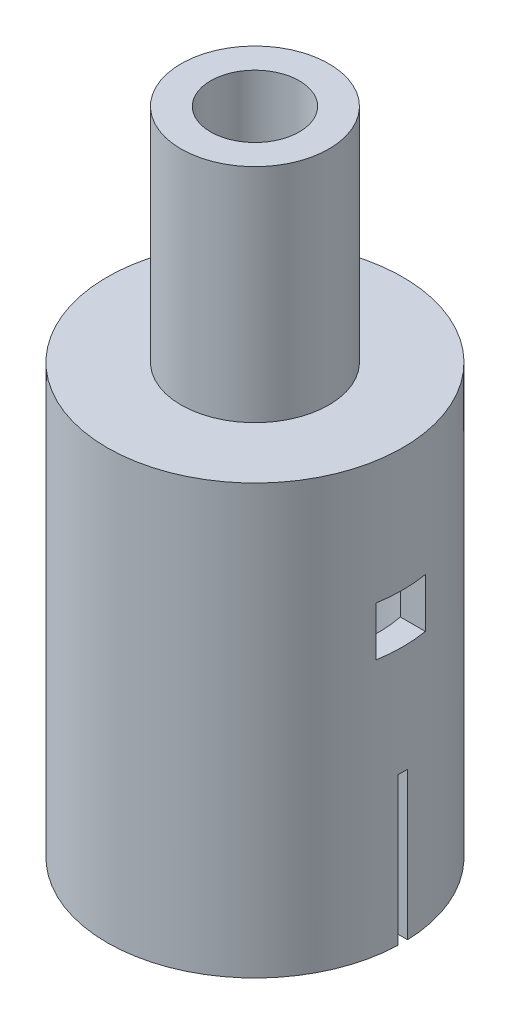
SolidWorks part; units mm, degrees
ref_plane "Front Plane" through (0, 0, 0) normal (0, 0, 1) x (1, 0, 0)
ref_plane "Top Plane" through (0, 0, 0) normal (0, 1, 0) x (1, 0, 0)
ref_plane "Right Plane" through (0, 0, 0) normal (1, 0, 0) x (0, 0, -1)
sketch "Sketch2" plane through (0, 0, 0) normal (0, 1, 0) x (1, 0, 0)
  circle A0 centre (0, 0) radius 7.62
  dimension "D1" = 15.24
extrude "Boss-Extrude1" add sketch "Sketch2" against normal blind 22.098 contours A0
sketch "Sketch3" plane through (0, -22.098, 0) normal (0, -1, 0) x (1, 0, 0)
  circle A0 centre (0, 0) radius 6.35
  dimension "D1" = 12.7
extrude "Cut-Extrude1" cut sketch "Sketch3" against normal blind 16.764
sketch "Sketch5" plane through (0, 0, 0) normal (0, 1, 0) x (1, 0, 0)
  circle A0 centre (0, 0) radius 2.3495
  dimension "D1" = 4.699
extrude "Cut-Extrude3" cut sketch "Sketch5" along normal blind 16.764 and the other way through all contours A0
sketch "Sketch6" plane through (0, 0, 0) normal (0, 1, 0) x (1, 0, 0)
  circle A0 centre (0, 0) radius 3.81
  dimension "D1" = 7.62
extrude "Boss-Extrude2" add sketch "Sketch6" along normal blind 11.43 contours A0
sketch "Sketch8" plane through (0, 11.43, 0) normal (0, 1, 0) x (1, 0, 0)
  circle A0 centre (0, 0) radius 2.286
  dimension "D1" = 4.572
extrude "Cut-Extrude4" cut sketch "Sketch8" against normal blind 11.176 contours A0
sketch "Sketch10" plane through (0, 0, 0) normal (0, -1, 0) x (1, 0, 0)
  circle A0 centre (0, 0) radius 1.7198
extrude "Cut-Extrude8" cut sketch "Sketch10" against normal up to next
sketch "Sketch12" plane through (0, 0, 0) normal (1, 0, 0) x (0, 0, -1)
  line L0 (7.62, 0) -> (-7.62, 0) construction
  line L1 (-1.27, -6.35) -> (1.27, -6.35)
  line L2 (-1.27, -6.35) -> (-1.27, -8.89)
  line L3 (-1.27, -8.89) -> (1.27, -8.89)
  line L4 (1.27, -6.35) -> (1.27, -8.89)
  line L5 (-1.27, -6.35) -> (1.27, -8.89) construction
  line L6 (-1.27, -8.89) -> (1.27, -6.35) construction
  point P0 (0, -7.62)
  dimension "D1" = 2.54
  dimension "D2" = 2.54
  dimension "D3" = 7.62
extrude "Cut-Extrude10" cut sketch "Sketch12" against normal through all both and the other way through all
sketch "Sketch16" plane through (0, -22.098, 0) normal (0, -1, 0) x (1, 0, 0)
  line L1 (-11.0491, -0.254) -> (11.0491, -0.254)
  line L2 (-11.0491, -0.254) -> (-11.0491, 0.254)
  line L3 (-11.0491, 0.254) -> (11.0491, 0.254)
  line L4 (11.0491, -0.254) -> (11.0491, 0.254)
  line L5 (-11.0491, -0.254) -> (11.0491, 0.254) construction
  line L6 (-11.0491, 0.254) -> (11.0491, -0.254) construction
  point P0 (0, 0)
  dimension "D1" = 0.508
extrude "Cut-Extrude16" cut sketch "Sketch16" against normal blind 7.62
